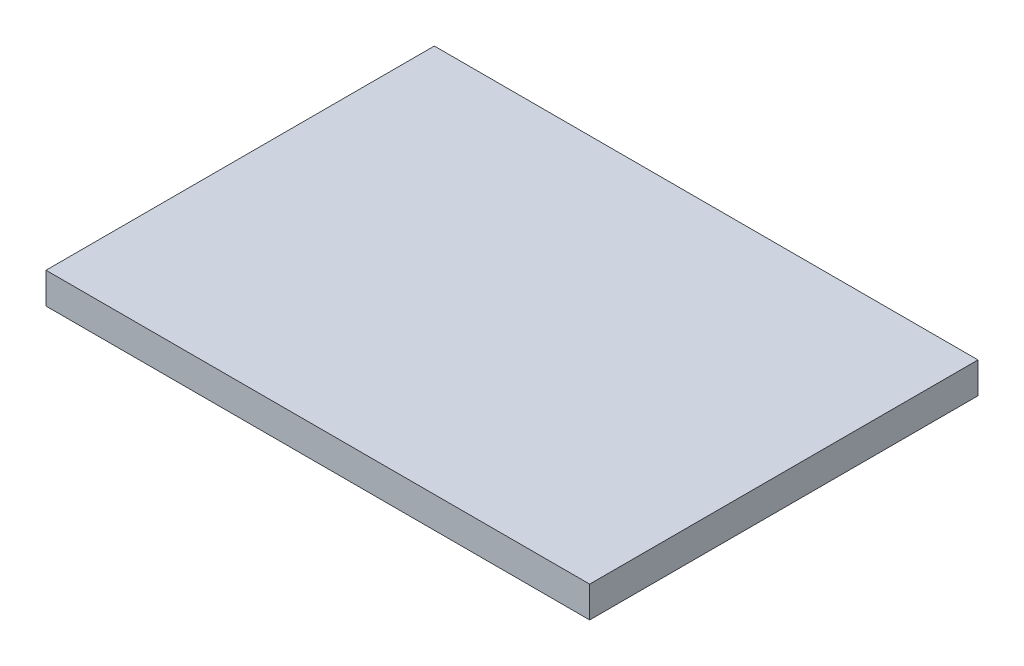
SolidWorks part; units mm, degrees
note: The reader was unsure of these and kept them because the rebuilt part matched: shared geometry of "Sketch7<3>", "Sketch8<7>", "Sketch8<8>".
ref_plane "Front Plane" through (0, 0, 0) normal (0, 0, 1) x (1, 0, 0)
ref_plane "Top Plane" through (0, 0, 0) normal (0, 1, 0) x (1, 0, 0)
ref_plane "Right Plane" through (0, 0, 0) normal (1, 0, 0) x (0, 0, -1)
sketch "Sketch7" plane through (0, 0, 0) normal (0, 1, 0) x (1, 0, 0)
  line L1 (-87.2062, 69.4355) -> (122.7938, 69.4355)
  line L2 (-87.2062, 69.4355) -> (-87.2062, -80.5645)
  line L3 (-87.2062, -80.5645) -> (122.7938, -80.5645)
  line L4 (122.7938, 69.4355) -> (122.7938, -80.5645)
  dimension "D1" = 210
  dimension "D2" = 150
extrude "Boss-Extrude1" add sketch "Sketch7" along normal blind 12
sketch "Sketch8" plane through (0, 12, 0) normal (0, 1, 0) x (1, 0, 0)
  line L0 (-84.7062, 36.9355) -> (-84.7062, 31.9355)
  line L1 (122.7938, 69.4355) -> (-87.2062, 69.4355) construction
  line L2 (-87.2062, -80.5645) -> (122.7938, -80.5645) construction
  line L3 (120.2938, 69.4355) -> (120.2938, -80.5645)
  line L4 (-59.7062, 54.4355) -> (-54.7062, 54.4355)
  line L5 (-84.7062, 46.9355) -> (-59.7062, 46.9355)
  line L6 (120.2938, 56.0051) -> (122.7938, 56.0051)
  line L7 (122.7938, -80.5645) -> (122.7938, 69.4355) construction
  line L8 (-84.7062, -80.5645) -> (-84.7062, -75.5645)
  line L9 (-84.7062, -75.5645) -> (-84.7062, -73.0645)
  line L10 (-84.7062, -73.0645) -> (-84.7062, -68.0645)
  line L11 (-84.7062, -68.0645) -> (-84.7062, -65.5645)
  line L12 (-84.7062, -65.5645) -> (-84.7062, -60.5645)
  line L13 (-84.7062, -60.5645) -> (-84.7062, -58.0645)
  line L14 (-84.7062, -58.0645) -> (-84.7062, -53.0645)
  line L15 (-84.7062, -53.0645) -> (-84.7062, -50.5645)
  line L16 (-84.7062, -50.5645) -> (-84.7062, -45.5645)
  line L17 (-84.7062, -45.5645) -> (-84.7062, -43.0645)
  line L18 (-84.7062, -43.0645) -> (-84.7062, -38.0645)
  line L19 (-84.7062, -38.0645) -> (-84.7062, -35.5645)
  line L20 (-84.7062, -35.5645) -> (-84.7062, -30.5645)
  line L21 (-84.7062, -30.5645) -> (-84.7062, -28.0645)
  line L22 (-84.7062, -28.0645) -> (-84.7062, -23.0645)
  line L23 (-84.7062, -23.0645) -> (-84.7062, -20.5645)
  line L24 (-84.7062, -20.5645) -> (-84.7062, -15.5645)
  line L25 (-84.7062, -15.5645) -> (-84.7062, -13.0645)
  line L26 (-84.7062, -13.0645) -> (-84.7062, -8.0645)
  line L27 (-84.7062, -8.0645) -> (-84.7062, -5.5645)
  line L28 (-84.7062, -5.5645) -> (-84.7062, -0.5645)
  line L29 (-84.7062, -0.5645) -> (-84.7062, 1.9355)
  line L30 (-84.7062, 1.9355) -> (-84.7062, 6.9355)
  line L31 (-84.7062, 6.9355) -> (-84.7062, 9.4355)
  line L32 (-84.7062, 9.4355) -> (-84.7062, 14.4355)
  line L33 (-84.7062, 14.4355) -> (-84.7062, 16.9355)
  line L34 (-84.7062, 16.9355) -> (-84.7062, 21.9355)
  line L35 (-84.7062, 21.9355) -> (-84.7062, 24.4355)
  line L36 (-84.7062, 24.4355) -> (-84.7062, 29.4355)
  line L37 (-84.7062, 29.4355) -> (-84.7062, 31.9355)
  line L38 (-84.7062, 36.9355) -> (-84.7062, 39.4355)
  line L39 (-84.7062, 39.4355) -> (-84.7062, 44.4355)
  line L40 (-84.7062, 44.4355) -> (-84.7062, 46.9355)
  line L41 (-84.7062, 46.9355) -> (-84.7062, 51.9355)
  line L42 (-84.7062, 51.9355) -> (-84.7062, 54.4355)
  line L43 (-84.7062, 54.4355) -> (-84.7062, 59.4355)
  line L44 (-84.7062, 54.4355) -> (-59.7062, 54.4355)
  line L45 (-84.7062, 54.4355) -> (-84.7062, 51.9355)
  line L46 (-84.7062, 51.9355) -> (-59.7062, 51.9355)
  line L47 (-59.7062, 54.4355) -> (-59.7062, 51.9355)
  line L48 (-84.7062, 46.9355) -> (-84.7062, 44.4355)
  line L49 (-84.7062, 44.4355) -> (-59.7062, 44.4355)
  line L50 (-59.7062, 46.9355) -> (-59.7062, 44.4355)
  line L51 (-84.7062, 39.4355) -> (-59.7062, 39.4355)
  line L52 (-84.7062, 39.4355) -> (-84.7062, 36.9355)
  line L53 (-84.7062, 36.9355) -> (-59.7062, 36.9355)
  line L54 (-59.7062, 39.4355) -> (-59.7062, 36.9355)
  line L55 (-84.7062, 31.9355) -> (-59.7062, 31.9355)
  line L56 (-84.7062, 31.9355) -> (-84.7062, 29.4355)
  line L57 (-84.7062, 29.4355) -> (-59.7062, 29.4355)
  line L58 (-59.7062, 31.9355) -> (-59.7062, 29.4355)
  line L59 (-84.7062, 24.4355) -> (-59.7062, 24.4355)
  line L60 (-84.7062, 24.4355) -> (-84.7062, 21.9355)
  line L61 (-84.7062, 21.9355) -> (-59.7062, 21.9355)
  line L62 (-59.7062, 24.4355) -> (-59.7062, 21.9355)
  line L63 (-84.7062, 16.9355) -> (-59.7062, 16.9355)
  line L64 (-84.7062, 16.9355) -> (-84.7062, 14.4355)
  line L65 (-84.7062, 14.4355) -> (-59.7062, 14.4355)
  line L66 (-59.7062, 16.9355) -> (-59.7062, 14.4355)
  line L67 (-84.7062, 9.4355) -> (-59.7062, 9.4355)
  line L68 (-84.7062, 9.4355) -> (-84.7062, 6.9355)
  line L69 (-84.7062, 6.9355) -> (-59.7062, 6.9355)
  line L70 (-59.7062, 9.4355) -> (-59.7062, 6.9355)
  line L71 (-84.7062, 1.9355) -> (-59.7062, 1.9355)
  line L72 (-84.7062, 1.9355) -> (-84.7062, -0.5645)
  line L73 (-84.7062, -0.5645) -> (-59.7062, -0.5645)
  line L74 (-59.7062, 1.9355) -> (-59.7062, -0.5645)
  line L75 (-84.7062, -5.5645) -> (-59.7062, -5.5645)
  line L76 (-84.7062, -5.5645) -> (-84.7062, -8.0645)
  line L77 (-84.7062, -8.0645) -> (-59.7062, -8.0645)
  line L78 (-59.7062, -5.5645) -> (-59.7062, -8.0645)
  line L79 (-84.7062, -13.0645) -> (-59.7062, -13.0645)
  line L80 (-84.7062, -13.0645) -> (-84.7062, -15.5645)
  line L81 (-84.7062, -15.5645) -> (-59.7062, -15.5645)
  line L82 (-59.7062, -13.0645) -> (-59.7062, -15.5645)
  line L83 (-84.7062, -20.5645) -> (-59.7062, -20.5645)
  line L84 (-84.7062, -20.5645) -> (-84.7062, -23.0645)
  line L85 (-84.7062, -23.0645) -> (-59.7062, -23.0645)
  line L86 (-59.7062, -20.5645) -> (-59.7062, -23.0645)
  line L87 (-84.7062, -28.0645) -> (-59.7062, -28.0645)
  line L88 (-84.7062, -28.0645) -> (-84.7062, -30.5645)
  line L89 (-84.7062, -30.5645) -> (-59.7062, -30.5645)
  line L90 (-59.7062, -28.0645) -> (-59.7062, -30.5645)
  line L91 (-84.7062, -35.5645) -> (-59.7062, -35.5645)
  line L92 (-84.7062, -35.5645) -> (-84.7062, -38.0645)
  line L93 (-84.7062, -38.0645) -> (-59.7062, -38.0645)
  line L94 (-59.7062, -35.5645) -> (-59.7062, -38.0645)
  line L95 (-84.7062, -43.0645) -> (-59.7062, -43.0645)
  line L96 (-84.7062, -43.0645) -> (-84.7062, -45.5645)
  line L97 (-84.7062, -45.5645) -> (-59.7062, -45.5645)
  line L98 (-59.7062, -43.0645) -> (-59.7062, -45.5645)
  line L99 (-84.7062, -50.5645) -> (-59.7062, -50.5645)
  line L100 (-84.7062, -50.5645) -> (-84.7062, -53.0645)
  line L101 (-84.7062, -53.0645) -> (-59.7062, -53.0645)
  line L102 (-59.7062, -50.5645) -> (-59.7062, -53.0645)
  line L103 (-84.7062, -58.0645) -> (-59.7062, -58.0645)
  line L104 (-84.7062, -58.0645) -> (-84.7062, -60.5645)
  line L105 (-84.7062, -60.5645) -> (-59.7062, -60.5645)
  line L106 (-59.7062, -58.0645) -> (-59.7062, -60.5645)
  line L107 (-29.7062, 54.4355) -> (-24.7062, 54.4355)
  line L108 (-54.7062, 54.4355) -> (-29.7062, 54.4355)
  line L109 (-54.7062, 54.4355) -> (-54.7062, 51.9355)
  line L110 (-54.7062, 51.9355) -> (-29.7062, 51.9355)
  line L111 (-29.7062, 54.4355) -> (-29.7062, 51.9355)
  line L112 (-54.7062, 46.9355) -> (-29.7062, 46.9355)
  line L113 (-54.7062, 46.9355) -> (-54.7062, 44.4355)
  line L114 (-54.7062, 44.4355) -> (-29.7062, 44.4355)
  line L115 (-29.7062, 46.9355) -> (-29.7062, 44.4355)
  line L116 (-54.7062, 39.4355) -> (-29.7062, 39.4355)
  line L117 (-54.7062, 39.4355) -> (-54.7062, 36.9355)
  line L118 (-54.7062, 36.9355) -> (-29.7062, 36.9355)
  line L119 (-29.7062, 39.4355) -> (-29.7062, 36.9355)
  line L120 (-54.7062, 31.9355) -> (-29.7062, 31.9355)
  line L121 (-54.7062, 31.9355) -> (-54.7062, 29.4355)
  line L122 (-54.7062, 29.4355) -> (-29.7062, 29.4355)
  line L123 (-29.7062, 31.9355) -> (-29.7062, 29.4355)
  line L124 (-54.7062, 24.4355) -> (-29.7062, 24.4355)
  line L125 (-54.7062, 24.4355) -> (-54.7062, 21.9355)
  line L126 (-54.7062, 21.9355) -> (-29.7062, 21.9355)
  line L127 (-29.7062, 24.4355) -> (-29.7062, 21.9355)
  line L128 (-54.7062, 16.9355) -> (-29.7062, 16.9355)
  line L129 (-54.7062, 16.9355) -> (-54.7062, 14.4355)
  line L130 (-54.7062, 14.4355) -> (-29.7062, 14.4355)
  line L131 (-29.7062, 16.9355) -> (-29.7062, 14.4355)
  line L132 (-54.7062, 9.4355) -> (-29.7062, 9.4355)
  line L133 (-54.7062, 9.4355) -> (-54.7062, 6.9355)
  line L134 (-54.7062, 6.9355) -> (-29.7062, 6.9355)
  line L135 (-29.7062, 9.4355) -> (-29.7062, 6.9355)
  line L136 (-54.7062, 1.9355) -> (-29.7062, 1.9355)
  line L137 (-54.7062, 1.9355) -> (-54.7062, -0.5645)
  line L138 (-54.7062, -0.5645) -> (-29.7062, -0.5645)
  line L139 (-29.7062, 1.9355) -> (-29.7062, -0.5645)
  line L140 (-54.7062, -5.5645) -> (-29.7062, -5.5645)
  line L141 (-54.7062, -5.5645) -> (-54.7062, -8.0645)
  line L142 (-54.7062, -8.0645) -> (-29.7062, -8.0645)
  line L143 (-29.7062, -5.5645) -> (-29.7062, -8.0645)
  line L144 (-54.7062, -13.0645) -> (-29.7062, -13.0645)
  line L145 (-54.7062, -13.0645) -> (-54.7062, -15.5645)
  line L146 (-54.7062, -15.5645) -> (-29.7062, -15.5645)
  line L147 (-29.7062, -13.0645) -> (-29.7062, -15.5645)
  line L148 (-54.7062, -20.5645) -> (-29.7062, -20.5645)
  line L149 (-54.7062, -20.5645) -> (-54.7062, -23.0645)
  line L150 (-54.7062, -23.0645) -> (-29.7062, -23.0645)
  line L151 (-29.7062, -20.5645) -> (-29.7062, -23.0645)
  line L152 (-54.7062, -28.0645) -> (-29.7062, -28.0645)
  line L153 (-54.7062, -28.0645) -> (-54.7062, -30.5645)
  line L154 (-54.7062, -30.5645) -> (-29.7062, -30.5645)
  line L155 (-29.7062, -28.0645) -> (-29.7062, -30.5645)
  line L156 (-54.7062, -35.5645) -> (-29.7062, -35.5645)
  line L157 (-54.7062, -35.5645) -> (-54.7062, -38.0645)
  line L158 (-54.7062, -38.0645) -> (-29.7062, -38.0645)
  line L159 (-29.7062, -35.5645) -> (-29.7062, -38.0645)
  line L160 (-54.7062, -43.0645) -> (-29.7062, -43.0645)
  line L161 (-54.7062, -43.0645) -> (-54.7062, -45.5645)
  line L162 (-54.7062, -45.5645) -> (-29.7062, -45.5645)
  line L163 (-29.7062, -43.0645) -> (-29.7062, -45.5645)
  line L164 (-54.7062, -50.5645) -> (-29.7062, -50.5645)
  line L165 (-54.7062, -50.5645) -> (-54.7062, -53.0645)
  line L166 (-54.7062, -53.0645) -> (-29.7062, -53.0645)
  line L167 (-29.7062, -50.5645) -> (-29.7062, -53.0645)
  line L168 (0.2938, 54.4355) -> (5.2938, 54.4355)
  line L169 (-24.7062, 54.4355) -> (0.2938, 54.4355)
  line L170 (-24.7062, 54.4355) -> (-24.7062, 51.9355)
  line L171 (-24.7062, 51.9355) -> (0.2938, 51.9355)
  line L172 (0.2938, 54.4355) -> (0.2938, 51.9355)
  line L173 (-24.7062, 46.9355) -> (0.2938, 46.9355)
  line L174 (-24.7062, 46.9355) -> (-24.7062, 44.4355)
  line L175 (-24.7062, 44.4355) -> (0.2938, 44.4355)
  line L176 (0.2938, 46.9355) -> (0.2938, 44.4355)
  line L177 (30.2938, 54.4355) -> (35.2938, 54.4355)
  line L178 (5.2938, 54.4355) -> (30.2938, 54.4355)
  line L179 (5.2938, 54.4355) -> (5.2938, 51.9355)
  line L180 (5.2938, 51.9355) -> (30.2938, 51.9355)
  line L181 (30.2938, 54.4355) -> (30.2938, 51.9355)
  line L182 (60.2938, 54.4355) -> (65.2938, 54.4355)
  line L183 (35.2938, 54.4355) -> (60.2938, 54.4355)
  line L184 (35.2938, 54.4355) -> (35.2938, 51.9355)
  line L185 (35.2938, 51.9355) -> (60.2938, 51.9355)
  line L186 (60.2938, 54.4355) -> (60.2938, 51.9355)
  line L187 (90.2938, 54.4355) -> (95.2938, 54.4355)
  line L188 (65.2938, 54.4355) -> (90.2938, 54.4355)
  line L189 (65.2938, 54.4355) -> (65.2938, 51.9355)
  line L190 (65.2938, 51.9355) -> (90.2938, 51.9355)
  line L191 (90.2938, 54.4355) -> (90.2938, 51.9355)
  line L192 (-84.7062, 59.4355) -> (-59.7062, 59.4355)
  line L193 (95.2938, 54.4355) -> (120.2938, 54.4355)
  line L194 (95.2938, 54.4355) -> (95.2938, 51.9355)
  line L195 (95.2938, 51.9355) -> (120.2938, 51.9355)
  line L196 (120.2938, 54.4355) -> (120.2938, 51.9355)
  line L197 (5.2938, 46.9355) -> (30.2938, 46.9355)
  line L198 (5.2938, 46.9355) -> (5.2938, 44.4355)
  line L199 (5.2938, 44.4355) -> (30.2938, 44.4355)
  line L200 (30.2938, 46.9355) -> (30.2938, 44.4355)
  line L201 (5.2938, 39.4355) -> (30.2938, 39.4355)
  line L202 (5.2938, 39.4355) -> (5.2938, 36.9355)
  line L203 (5.2938, 36.9355) -> (30.2938, 36.9355)
  line L204 (30.2938, 39.4355) -> (30.2938, 36.9355)
  line L205 (5.2938, 31.9355) -> (30.2938, 31.9355)
  line L206 (5.2938, 31.9355) -> (5.2938, 29.4355)
  line L207 (5.2938, 29.4355) -> (30.2938, 29.4355)
  line L208 (30.2938, 31.9355) -> (30.2938, 29.4355)
  line L209 (5.2938, 24.4355) -> (30.2938, 24.4355)
  line L210 (5.2938, 24.4355) -> (5.2938, 21.9355)
  line L211 (5.2938, 21.9355) -> (30.2938, 21.9355)
  line L212 (30.2938, 24.4355) -> (30.2938, 21.9355)
  line L213 (5.2938, 16.9355) -> (30.2938, 16.9355)
  line L214 (5.2938, 16.9355) -> (5.2938, 14.4355)
  line L215 (5.2938, 14.4355) -> (30.2938, 14.4355)
  line L216 (30.2938, 16.9355) -> (30.2938, 14.4355)
  line L217 (5.2938, 9.4355) -> (30.2938, 9.4355)
  line L218 (5.2938, 9.4355) -> (5.2938, 6.9355)
  line L219 (5.2938, 6.9355) -> (30.2938, 6.9355)
  line L220 (30.2938, 9.4355) -> (30.2938, 6.9355)
  line L221 (5.2938, 1.9355) -> (30.2938, 1.9355)
  line L222 (5.2938, 1.9355) -> (5.2938, -0.5645)
  line L223 (5.2938, -0.5645) -> (30.2938, -0.5645)
  line L224 (30.2938, 1.9355) -> (30.2938, -0.5645)
  line L225 (5.2938, -5.5645) -> (30.2938, -5.5645)
  line L226 (5.2938, -5.5645) -> (5.2938, -8.0645)
  line L227 (5.2938, -8.0645) -> (30.2938, -8.0645)
  line L228 (30.2938, -5.5645) -> (30.2938, -8.0645)
  line L229 (5.2938, -13.0645) -> (30.2938, -13.0645)
  line L230 (5.2938, -13.0645) -> (5.2938, -15.5645)
  line L231 (5.2938, -15.5645) -> (30.2938, -15.5645)
  line L232 (30.2938, -13.0645) -> (30.2938, -15.5645)
  line L233 (5.2938, -20.5645) -> (30.2938, -20.5645)
  line L234 (5.2938, -20.5645) -> (5.2938, -23.0645)
  line L235 (5.2938, -23.0645) -> (30.2938, -23.0645)
  line L236 (30.2938, -20.5645) -> (30.2938, -23.0645)
  line L237 (5.2938, -28.0645) -> (30.2938, -28.0645)
  line L238 (5.2938, -28.0645) -> (5.2938, -30.5645)
  line L239 (5.2938, -30.5645) -> (30.2938, -30.5645)
  line L240 (30.2938, -28.0645) -> (30.2938, -30.5645)
  line L241 (5.2938, -35.5645) -> (30.2938, -35.5645)
  line L242 (5.2938, -35.5645) -> (5.2938, -38.0645)
  line L243 (5.2938, -38.0645) -> (30.2938, -38.0645)
  line L244 (30.2938, -35.5645) -> (30.2938, -38.0645)
  line L245 (5.2938, -43.0645) -> (30.2938, -43.0645)
  line L246 (5.2938, -43.0645) -> (5.2938, -45.5645)
  line L247 (5.2938, -45.5645) -> (30.2938, -45.5645)
  line L248 (30.2938, -43.0645) -> (30.2938, -45.5645)
  line L249 (5.2938, -50.5645) -> (30.2938, -50.5645)
  line L250 (5.2938, -50.5645) -> (5.2938, -53.0645)
  line L251 (5.2938, -53.0645) -> (30.2938, -53.0645)
  line L252 (30.2938, -50.5645) -> (30.2938, -53.0645)
  line L253 (5.2938, -58.0645) -> (30.2938, -58.0645)
  line L254 (5.2938, -58.0645) -> (5.2938, -60.5645)
  line L255 (5.2938, -60.5645) -> (30.2938, -60.5645)
  line L256 (30.2938, -58.0645) -> (30.2938, -60.5645)
  line L257 (5.2938, -65.5645) -> (30.2938, -65.5645)
  line L258 (5.2938, -65.5645) -> (5.2938, -68.0645)
  line L259 (5.2938, -68.0645) -> (30.2938, -68.0645)
  line L260 (30.2938, -65.5645) -> (30.2938, -68.0645)
  line L261 (5.2938, -73.0645) -> (30.2938, -73.0645)
  line L262 (5.2938, -73.0645) -> (5.2938, -75.5645)
  line L263 (5.2938, -75.5645) -> (30.2938, -75.5645)
  line L264 (30.2938, -73.0645) -> (30.2938, -75.5645)
  line L265 (35.2938, 46.9355) -> (60.2938, 46.9355)
  line L266 (35.2938, 46.9355) -> (35.2938, 44.4355)
  line L267 (35.2938, 44.4355) -> (60.2938, 44.4355)
  line L268 (60.2938, 46.9355) -> (60.2938, 44.4355)
  line L269 (65.2938, 46.9355) -> (90.2938, 46.9355)
  line L270 (65.2938, 46.9355) -> (65.2938, 44.4355)
  line L271 (65.2938, 44.4355) -> (90.2938, 44.4355)
  line L272 (90.2938, 46.9355) -> (90.2938, 44.4355)
  line L273 (65.2938, 39.4355) -> (90.2938, 39.4355)
  line L274 (65.2938, 39.4355) -> (65.2938, 36.9355)
  line L275 (65.2938, 36.9355) -> (90.2938, 36.9355)
  line L276 (90.2938, 39.4355) -> (90.2938, 36.9355)
  line L277 (65.2938, 31.9355) -> (90.2938, 31.9355)
  line L278 (65.2938, 31.9355) -> (65.2938, 29.4355)
  line L279 (65.2938, 29.4355) -> (90.2938, 29.4355)
  line L280 (90.2938, 31.9355) -> (90.2938, 29.4355)
  line L281 (65.2938, 24.4355) -> (90.2938, 24.4355)
  line L282 (65.2938, 24.4355) -> (65.2938, 21.9355)
  line L283 (65.2938, 21.9355) -> (90.2938, 21.9355)
  line L284 (90.2938, 24.4355) -> (90.2938, 21.9355)
  line L285 (65.2938, 16.9355) -> (90.2938, 16.9355)
  line L286 (65.2938, 16.9355) -> (65.2938, 14.4355)
  line L287 (65.2938, 14.4355) -> (90.2938, 14.4355)
  line L288 (90.2938, 16.9355) -> (90.2938, 14.4355)
  line L289 (65.2938, 9.4355) -> (90.2938, 9.4355)
  line L290 (65.2938, 9.4355) -> (65.2938, 6.9355)
  line L291 (65.2938, 6.9355) -> (90.2938, 6.9355)
  line L292 (90.2938, 9.4355) -> (90.2938, 6.9355)
  line L293 (65.2938, 1.9355) -> (90.2938, 1.9355)
  line L294 (65.2938, 1.9355) -> (65.2938, -0.5645)
  line L295 (65.2938, -0.5645) -> (90.2938, -0.5645)
  line L296 (90.2938, 1.9355) -> (90.2938, -0.5645)
  line L297 (65.2938, -5.5645) -> (90.2938, -5.5645)
  line L298 (65.2938, -5.5645) -> (65.2938, -8.0645)
  line L299 (65.2938, -8.0645) -> (90.2938, -8.0645)
  line L300 (90.2938, -5.5645) -> (90.2938, -8.0645)
  line L301 (65.2938, -13.0645) -> (90.2938, -13.0645)
  line L302 (65.2938, -13.0645) -> (65.2938, -15.5645)
  line L303 (65.2938, -15.5645) -> (90.2938, -15.5645)
  line L304 (90.2938, -13.0645) -> (90.2938, -15.5645)
  line L305 (65.2938, -20.5645) -> (90.2938, -20.5645)
  line L306 (65.2938, -20.5645) -> (65.2938, -23.0645)
  line L307 (65.2938, -23.0645) -> (90.2938, -23.0645)
  line L308 (90.2938, -20.5645) -> (90.2938, -23.0645)
  line L309 (65.2938, -28.0645) -> (90.2938, -28.0645)
  line L310 (65.2938, -28.0645) -> (65.2938, -30.5645)
  line L311 (65.2938, -30.5645) -> (90.2938, -30.5645)
  line L312 (90.2938, -28.0645) -> (90.2938, -30.5645)
  line L313 (65.2938, -35.5645) -> (90.2938, -35.5645)
  line L314 (65.2938, -35.5645) -> (65.2938, -38.0645)
  line L315 (65.2938, -38.0645) -> (90.2938, -38.0645)
  line L316 (90.2938, -35.5645) -> (90.2938, -38.0645)
  line L317 (65.2938, -43.0645) -> (90.2938, -43.0645)
  line L318 (65.2938, -43.0645) -> (65.2938, -45.5645)
  line L319 (65.2938, -45.5645) -> (90.2938, -45.5645)
  line L320 (90.2938, -43.0645) -> (90.2938, -45.5645)
  line L321 (65.2938, -50.5645) -> (90.2938, -50.5645)
  line L322 (65.2938, -50.5645) -> (65.2938, -53.0645)
  line L323 (65.2938, -53.0645) -> (90.2938, -53.0645)
  line L324 (90.2938, -50.5645) -> (90.2938, -53.0645)
  line L325 (65.2938, -58.0645) -> (90.2938, -58.0645)
  line L326 (65.2938, -58.0645) -> (65.2938, -60.5645)
  line L327 (65.2938, -60.5645) -> (90.2938, -60.5645)
  line L328 (90.2938, -58.0645) -> (90.2938, -60.5645)
  line L329 (95.2938, 46.9355) -> (120.2938, 46.9355)
  line L330 (95.2938, 46.9355) -> (95.2938, 44.4355)
  line L331 (95.2938, 44.4355) -> (120.2938, 44.4355)
  line L332 (120.2938, 46.9355) -> (120.2938, 44.4355)
  line L333 (95.2938, 39.4355) -> (120.2938, 39.4355)
  line L334 (95.2938, 39.4355) -> (95.2938, 36.9355)
  line L335 (95.2938, 36.9355) -> (120.2938, 36.9355)
  line L336 (120.2938, 39.4355) -> (120.2938, 36.9355)
  line L337 (95.2938, 31.9355) -> (120.2938, 31.9355)
  line L338 (95.2938, 31.9355) -> (95.2938, 29.4355)
  line L339 (95.2938, 29.4355) -> (120.2938, 29.4355)
  line L340 (120.2938, 31.9355) -> (120.2938, 29.4355)
  line L341 (95.2938, 24.4355) -> (120.2938, 24.4355)
  line L342 (95.2938, 24.4355) -> (95.2938, 21.9355)
  line L343 (95.2938, 21.9355) -> (120.2938, 21.9355)
  line L344 (120.2938, 24.4355) -> (120.2938, 21.9355)
  line L345 (95.2938, 16.9355) -> (120.2938, 16.9355)
  line L346 (95.2938, 16.9355) -> (95.2938, 14.4355)
  line L347 (95.2938, 14.4355) -> (120.2938, 14.4355)
  line L348 (120.2938, 16.9355) -> (120.2938, 14.4355)
  line L349 (95.2938, 9.4355) -> (120.2938, 9.4355)
  line L350 (95.2938, 9.4355) -> (95.2938, 6.9355)
  line L351 (95.2938, 6.9355) -> (120.2938, 6.9355)
  line L352 (120.2938, 9.4355) -> (120.2938, 6.9355)
  line L353 (95.2938, 1.9355) -> (120.2938, 1.9355)
  line L354 (95.2938, 1.9355) -> (95.2938, -0.5645)
  line L355 (95.2938, -0.5645) -> (120.2938, -0.5645)
  line L356 (120.2938, 1.9355) -> (120.2938, -0.5645)
  line L357 (95.2938, -5.5645) -> (120.2938, -5.5645)
  line L358 (95.2938, -5.5645) -> (95.2938, -8.0645)
  line L359 (95.2938, -8.0645) -> (120.2938, -8.0645)
  line L360 (120.2938, -5.5645) -> (120.2938, -8.0645)
  line L361 (95.2938, -13.0645) -> (120.2938, -13.0645)
  line L362 (95.2938, -13.0645) -> (95.2938, -15.5645)
  line L363 (95.2938, -15.5645) -> (120.2938, -15.5645)
  line L364 (120.2938, -13.0645) -> (120.2938, -15.5645)
  line L365 (-54.7062, 59.4355) -> (-29.7062, 59.4355)
  line L366 (-24.7062, 59.4355) -> (0.2938, 59.4355)
  line L367 (5.2938, 59.4355) -> (30.2938, 59.4355)
  line L368 (35.2938, 59.4355) -> (60.2938, 59.4355)
  line L369 (65.2938, 59.4355) -> (90.2938, 59.4355)
  line L370 (95.2938, 59.4355) -> (120.2938, 59.4355)
  text T0 "<b>ABS</b>" font "Century Gothic" height 6
  text T1 "<b>PETG BASIC</b>" font "Century Gothic" height 4
  text T2 "<b>PETG CF</b>" font "Century Gothic" height 5
  text T3 "<b>PLA BASIC</b>" font "Century Gothic" height 4
  text T4 "<b>PLA CF</b>" font "Century Gothic" height 5
  text T5 "<b>PLA MATTE</b>" font "Century Gothic" height 3.5
  text T6 "<b>PLA TOUGH</b>" font "Century Gothic" height 3.5
  dimension "D1" = 25
  dimension "D2" = 2.5
  dimension "D3" = 5
  dimension "D4" = 2.5
  dimension "D5" = 5
  dimension "D6" = 25
  dimension "D7" = 5
  dimension "D8" = 25
  dimension "D9" = 5
  dimension "D10" = 25
  dimension "D11" = 5
  dimension "D12" = 25
  dimension "D13" = 5
  dimension "D14" = 25
  dimension "D15" = 5
  dimension "D16" = 25
extrude "Boss-Extrude3" add sketch "Sketch7<3>" along normal blind 10 separate body
sketch "Sketch7<3>" plane through (0, 0, 0) normal (0, 1, 0) x (1, 0, 0) same geometry as "Sketch7"
extrude "Cut-Extrude1" cut sketch "Sketch8" against normal blind 10 contours L47 L44 L42 L46 | L50 L5 L40 L49 | L54 L51 L38 L53 | L58 L55 L37 L57 | L62 L59 L35 L61 | L66 L63 L33 L65 | L70 L67 L31 L69 | L74 L71 L29 L73 | L78 L75 L27 L77 | L82 L79 L25 L81 | L86 L83 L23 L85 | L90 L87 L21 L89 | L94 L91 L19 L93 | L98 L95 L17 L97 | L102 L99 L15 L101 | L106 L103 L13 L105 | L167 L164 L165 L166 | L163 L160 L161 L162 | L159 L156 L157 L158 | L155 L152 L153 L154 | L151 L148 L149 L150 | L147 L144 L145 L146 | L143 L140 L141 L142 | L139 L136 L137 L138 | L135 L132 L133 L134 | L131 L128 L129 L130 | L127 L124 L125 L126 | L123 L120 L121 L122 | L119 L116 L117 L118 | L115 L112 L113 L114 | L111 L108 L109 L110 | L172 L169 L170 L171 | L176 L173 L174 L175
extrude "Cut-Extrude2" cut sketch "Sketch8<7>" against normal blind 10 contours L181 L178 L179 L180 | L200 L197 L198 L199 | L204 L201 L202 L203 | L208 L205 L206 L207 | L212 L209 L210 L211 | L216 L213 L214 L215 | L220 L217 L218 L219 | L224 L221 L222 L223 | L228 L225 L226 L227 | L232 L229 L230 L231 | L236 L233 L234 L235 | L240 L237 L238 L239 | L244 L241 L242 L243 | L248 L245 L246 L247 | L252 L249 L250 L251 | L256 L253 L254 L255 | L260 L257 L258 L259 | L264 L261 L262 L263 | L186 L183 L184 L185 | L268 L265 L266 L267 | L191 L188 L189 L190 | L272 L269 L270 L271 | L276 L273 L274 L275 | L280 L277 L278 L279 | L284 L281 L282 L283 | L288 L285 L286 L287 | L292 L289 L290 L291 | L296 L293 L294 L295 | L300 L297 L298 L299 | L304 L301 L302 L303 | L308 L305 L306 L307 | L312 L309 L310 L311 | L316 L313 L314 L315 | L320 L317 L318 L319 | L324 L321 L322 L323 | L328 L325 L326 L327
sketch "Sketch8<7>" plane through (0, 12, 0) normal (0, 1, 0) x (1, 0, 0) same geometry as "Sketch8"
extrude "Cut-Extrude3" cut sketch "Sketch8<8>" against normal blind 10 contours L194 L195 L3 L193 | L330 L331 L3 L329 | L334 L335 L3 L333 | L338 L339 L3 L337 | L342 L343 L3 L341 | L346 L347 L3 L345 | L350 L351 L3 L349 | L354 L355 L3 L353 | L358 L359 L3 L357 | L362 L363 L3 L361
sketch "Sketch8<8>" plane through (0, 12, 0) normal (0, 1, 0) x (1, 0, 0) same geometry as "Sketch8"
fillet "Fillet1" radius 16 4 edges at (122.7938, 5, -69.4355) (122.7938, 5, 80.5645) (-87.2062, 5, 80.5645) (-87.2062, 5, -69.4355)
fillet "Fillet4" radius 2 8 edges at (-82.5199, 10, 75.8782) (-87.2062, 10, 5.5645) (-82.5199, 10, -64.7492) (17.7938, 10, -69.4355) (118.1075, 10, -64.7492) (122.7938, 10, 5.5645) (118.1075, 10, 75.8782) (17.7938, 10, 80.5645)
